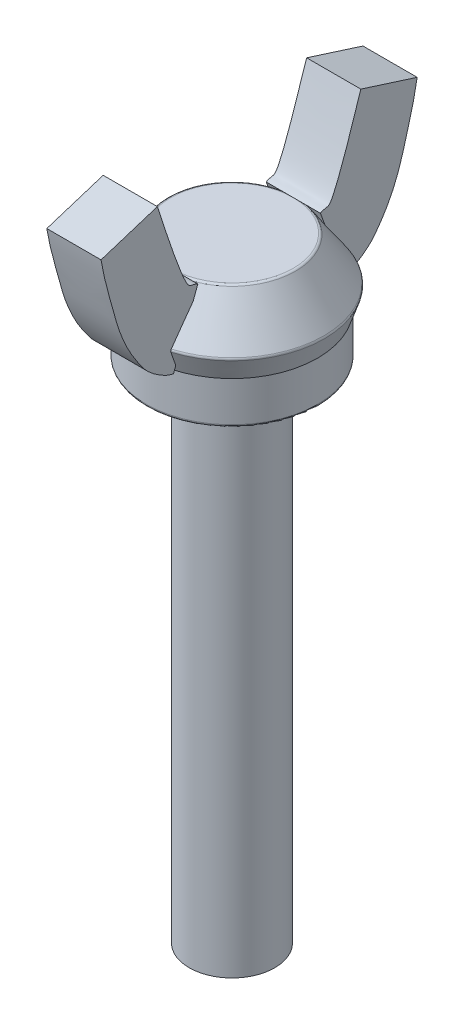
SolidWorks part; units mm, degrees
ref_plane "정면" through (0, 0, 0) normal (0, 0, 1) x (1, 0, 0)
ref_plane "윗면" through (0, 0, 0) normal (0, 1, 0) x (1, 0, 0)
ref_plane "우측면" through (0, 0, 0) normal (1, 0, 0) x (0, 0, -1)
sketch "스케치1" plane through (0, 0, 0) normal (0, 1, 0) x (1, 0, 0)
  circle A0 centre (0, 0) radius 3
  dimension "D1" = 6
extrude "보스-돌출1" add sketch "스케치1" along normal blind 35.5
sketch "스케치2" plane through (0, 35.5, 0) normal (0, 1, 0) x (1, 0, 0)
  circle A0 centre (0, 0) radius 6
  dimension "D1" = 12
extrude "보스-돌출2" add sketch "스케치2" along normal blind 3
sketch "스케치3" plane through (0, 0, 0) normal (1, 0, 0) x (0, 0, -1)
  line L0 (0, 38.5) -> (0, 43.1) construction
  line L1 (6, 38.5) -> (-6, 38.5) construction
  line L2 (0, 43.1) -> (4.4, 43.1)
  line L3 (6.5, 40) -> (4.4, 43.1)
  line L5 (6.5, 40) -> (6, 38.5)
  line L6 (6, 35.5) -> (6, 38.5) construction
  line L7 (6, 38.5) -> (0, 38.5)
  line L8 (0, 38.5) -> (0, 43.1)
  dimension "D1" = 4.4
  dimension "D2" = 1.5
  dimension "D3" = 0.5
  dimension "D4" = 4.6
revolve "회전1" add sketch "스케치3" angle 360 about L0
fillet "필렛1" radius 0.2 3 edges at (0, 43.1, -4.4) (0, 40, -6.5) (0, 35.5, 6)
sketch "스케치4" plane through (0, 0, 0) normal (1, 0, 0) x (0, 0, -1)
  line L0 (7.1297, 49.2161) -> (11.0781, 47.9584)
  line L1 (0, 43.1) -> (0, 47.7399) construction
  line L2 (-6, 38.5) -> (6, 38.5) construction
  line L3 (4.2939, 43.1) -> (6, 38.5)
  line L4 (4.2939, 43.1) -> (-4.2939, 43.1) construction
  line L5 (-4.2939, 43.1) -> (-6, 38.5)
  line L6 (-7.1297, 49.2161) -> (-11.0781, 47.9584)
  spline S0 degree 3 poles (4.2939, 43.1) (4.7038, 43.32) (4.9932, 42.7684) (6.2937, 46.6118) (7.1297, 49.2161) knots 0 0 0 0 0.337976 1 1 1 1
  spline S1 degree 3 poles (11.0781, 47.9584) (10.8477, 46.5685) (10.4498, 45.3023) (9.9074, 43.2608) (9.3113, 41.6663) (8.2355, 40.0212) (7.6198, 39.2862) (6.4952, 38.5935) (6, 38.5) knots 0 0 0 0 0.303157 0.355873 0.527166 0.682348 0.853387 1 1 1 1
  spline S2 degree 3 poles (-11.0781, 47.9584) (-10.8477, 46.5685) (-10.4498, 45.3023) (-9.9074, 43.2608) (-9.3113, 41.6663) (-8.2355, 40.0212) (-7.6198, 39.2862) (-6.4952, 38.5935) (-6, 38.5) knots 0 0 0 0 0.303157 0.355873 0.527166 0.682348 0.853387 1 1 1 1
  spline S3 degree 3 poles (-4.2939, 43.1) (-4.7038, 43.32) (-4.9932, 42.7684) (-6.2937, 46.6118) (-7.1297, 49.2161) knots 0 0 0 0 0.337976 1 1 1 1
extrude "보스-돌출3" add sketch "스케치4" along normal blind 1.9 and the other way blind 1.9
